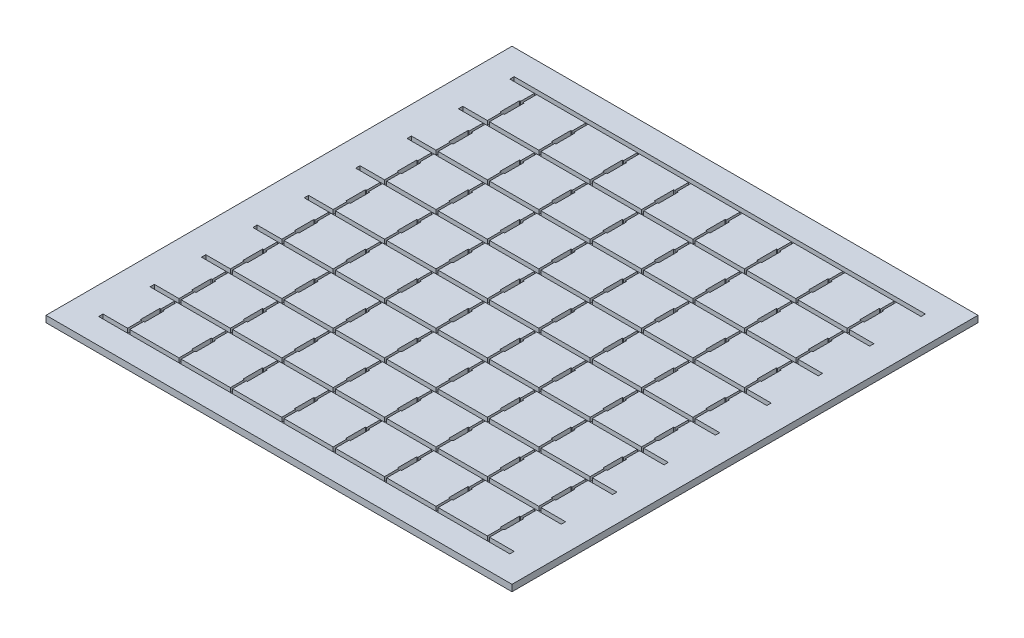
SolidWorks part; units mm, degrees
material "Acrylic (Medium-high impact)"
ref_plane "Front Plane" through (0, 0, 0) normal (0, 0, 1) x (1, 0, 0)
ref_plane "Top Plane" through (0, 0, 0) normal (0, 1, 0) x (1, 0, 0)
ref_plane "Right Plane" through (0, 0, 0) normal (1, 0, 0) x (0, 0, -1)
sketch "Sketch1" plane through (0, 0, 0) normal (0, 1, 0) x (1, 0, 0)
  line L1 (0, 0) -> (431.8, 0)
  line L2 (0, 0) -> (0, 431.8)
  line L3 (0, 431.8) -> (431.8, 431.8)
  line L4 (431.8, 0) -> (431.8, 431.8)
  dimension "D1" = 431.8
  dimension "D2" = 431.8
extrude "Boss-Extrude1" add sketch "Sketch1" along normal blind 6
sketch "Sketch2" plane through (0, 6, 0) normal (0, 1, 0) x (1, 0, 0)
  line L0 (73.025, 25.4) -> (73.025, 73.025) construction
  line L1 (25.4, 25.4) -> (73.025, 25.4) construction
  line L2 (25.4, 25.4) -> (25.4, 73.025) construction
  line L3 (25.4, 73.025) -> (73.025, 73.025) construction
  line L4 (73.025, 25.4) -> (73.025, 73.025) construction
  line L5 (73.025, 25.4) -> (120.65, 25.4) construction
  line L6 (120.65, 25.4) -> (120.65, 73.025) construction
  line L7 (73.025, 73.025) -> (120.65, 73.025) construction
  line L8 (120.65, 25.4) -> (120.65, 73.025) construction
  line L9 (120.65, 25.4) -> (168.275, 25.4) construction
  line L10 (168.275, 25.4) -> (168.275, 73.025) construction
  line L11 (120.65, 73.025) -> (168.275, 73.025) construction
  line L12 (168.275, 25.4) -> (168.275, 73.025) construction
  line L13 (168.275, 25.4) -> (215.9, 25.4) construction
  line L14 (215.9, 25.4) -> (215.9, 73.025) construction
  line L15 (168.275, 73.025) -> (215.9, 73.025) construction
  line L16 (215.9, 25.4) -> (215.9, 73.025) construction
  line L17 (215.9, 25.4) -> (263.525, 25.4) construction
  line L18 (263.525, 25.4) -> (263.525, 73.025) construction
  line L19 (215.9, 73.025) -> (263.525, 73.025) construction
  line L20 (263.525, 25.4) -> (263.525, 73.025) construction
  line L21 (263.525, 25.4) -> (311.15, 25.4) construction
  line L22 (311.15, 25.4) -> (311.15, 73.025) construction
  line L23 (263.525, 73.025) -> (311.15, 73.025) construction
  line L24 (311.15, 25.4) -> (311.15, 73.025) construction
  line L25 (311.15, 25.4) -> (358.775, 25.4) construction
  line L26 (358.775, 25.4) -> (358.775, 73.025) construction
  line L27 (311.15, 73.025) -> (358.775, 73.025) construction
  line L28 (358.775, 25.4) -> (358.775, 73.025) construction
  line L29 (358.775, 25.4) -> (406.4, 25.4) construction
  line L30 (406.4, 25.4) -> (406.4, 73.025) construction
  line L31 (358.775, 73.025) -> (406.4, 73.025) construction
  line L32 (73.025, 73.025) -> (73.025, 120.65) construction
  line L33 (73.025, 73.025) -> (120.65, 73.025) construction
  line L34 (120.65, 73.025) -> (120.65, 120.65) construction
  line L35 (73.025, 120.65) -> (120.65, 120.65) construction
  line L36 (120.65, 73.025) -> (120.65, 120.65) construction
  line L37 (120.65, 73.025) -> (168.275, 73.025) construction
  line L38 (168.275, 73.025) -> (168.275, 120.65) construction
  line L39 (120.65, 120.65) -> (168.275, 120.65) construction
  line L40 (168.275, 73.025) -> (168.275, 120.65) construction
  line L41 (168.275, 73.025) -> (215.9, 73.025) construction
  line L42 (215.9, 73.025) -> (215.9, 120.65) construction
  line L43 (168.275, 120.65) -> (215.9, 120.65) construction
  line L44 (215.9, 73.025) -> (215.9, 120.65) construction
  line L45 (215.9, 73.025) -> (263.525, 73.025) construction
  line L46 (263.525, 73.025) -> (263.525, 120.65) construction
  line L47 (215.9, 120.65) -> (263.525, 120.65) construction
  line L48 (263.525, 73.025) -> (263.525, 120.65) construction
  line L49 (263.525, 73.025) -> (311.15, 73.025) construction
  line L50 (311.15, 73.025) -> (311.15, 120.65) construction
  line L51 (263.525, 120.65) -> (311.15, 120.65) construction
  line L52 (311.15, 73.025) -> (311.15, 120.65) construction
  line L53 (311.15, 73.025) -> (358.775, 73.025) construction
  line L54 (358.775, 73.025) -> (358.775, 120.65) construction
  line L55 (311.15, 120.65) -> (358.775, 120.65) construction
  line L56 (358.775, 73.025) -> (358.775, 120.65) construction
  line L57 (358.775, 73.025) -> (406.4, 73.025) construction
  line L58 (406.4, 73.025) -> (406.4, 120.65) construction
  line L59 (358.775, 120.65) -> (406.4, 120.65) construction
  line L60 (73.025, 120.65) -> (73.025, 168.275) construction
  line L61 (73.025, 120.65) -> (120.65, 120.65) construction
  line L62 (120.65, 120.65) -> (120.65, 168.275) construction
  line L63 (73.025, 168.275) -> (120.65, 168.275) construction
  line L64 (120.65, 120.65) -> (120.65, 168.275) construction
  line L65 (120.65, 120.65) -> (168.275, 120.65) construction
  line L66 (168.275, 120.65) -> (168.275, 168.275) construction
  line L67 (120.65, 168.275) -> (168.275, 168.275) construction
  line L68 (168.275, 120.65) -> (168.275, 168.275) construction
  line L69 (168.275, 120.65) -> (215.9, 120.65) construction
  line L70 (215.9, 120.65) -> (215.9, 168.275) construction
  line L71 (168.275, 168.275) -> (215.9, 168.275) construction
  line L72 (215.9, 120.65) -> (215.9, 168.275) construction
  line L73 (215.9, 120.65) -> (263.525, 120.65) construction
  line L74 (263.525, 120.65) -> (263.525, 168.275) construction
  line L75 (215.9, 168.275) -> (263.525, 168.275) construction
  line L76 (263.525, 120.65) -> (263.525, 168.275) construction
  line L77 (263.525, 120.65) -> (311.15, 120.65) construction
  line L78 (311.15, 120.65) -> (311.15, 168.275) construction
  line L79 (263.525, 168.275) -> (311.15, 168.275) construction
  line L80 (311.15, 120.65) -> (311.15, 168.275) construction
  line L81 (311.15, 120.65) -> (358.775, 120.65) construction
  line L82 (358.775, 120.65) -> (358.775, 168.275) construction
  line L83 (311.15, 168.275) -> (358.775, 168.275) construction
  line L84 (358.775, 120.65) -> (358.775, 168.275) construction
  line L85 (358.775, 120.65) -> (406.4, 120.65) construction
  line L86 (406.4, 120.65) -> (406.4, 168.275) construction
  line L87 (358.775, 168.275) -> (406.4, 168.275) construction
  line L88 (73.025, 168.275) -> (73.025, 215.9) construction
  line L89 (73.025, 168.275) -> (120.65, 168.275) construction
  line L90 (120.65, 168.275) -> (120.65, 215.9) construction
  line L91 (73.025, 215.9) -> (120.65, 215.9) construction
  line L92 (120.65, 168.275) -> (120.65, 215.9) construction
  line L93 (120.65, 168.275) -> (168.275, 168.275) construction
  line L94 (168.275, 168.275) -> (168.275, 215.9) construction
  line L95 (120.65, 215.9) -> (168.275, 215.9) construction
  line L96 (168.275, 168.275) -> (168.275, 215.9) construction
  line L97 (168.275, 168.275) -> (215.9, 168.275) construction
  line L98 (215.9, 168.275) -> (215.9, 215.9) construction
  line L99 (168.275, 215.9) -> (215.9, 215.9) construction
  line L100 (215.9, 168.275) -> (215.9, 215.9) construction
  line L101 (215.9, 168.275) -> (263.525, 168.275) construction
  line L102 (263.525, 168.275) -> (263.525, 215.9) construction
  line L103 (215.9, 215.9) -> (263.525, 215.9) construction
  line L104 (263.525, 168.275) -> (263.525, 215.9) construction
  line L105 (263.525, 168.275) -> (311.15, 168.275) construction
  line L106 (311.15, 168.275) -> (311.15, 215.9) construction
  line L107 (263.525, 215.9) -> (311.15, 215.9) construction
  line L108 (311.15, 168.275) -> (311.15, 215.9) construction
  line L109 (311.15, 168.275) -> (358.775, 168.275) construction
  line L110 (358.775, 168.275) -> (358.775, 215.9) construction
  line L111 (311.15, 215.9) -> (358.775, 215.9) construction
  line L112 (358.775, 168.275) -> (358.775, 215.9) construction
  line L113 (358.775, 168.275) -> (406.4, 168.275) construction
  line L114 (406.4, 168.275) -> (406.4, 215.9) construction
  line L115 (358.775, 215.9) -> (406.4, 215.9) construction
  line L116 (73.025, 215.9) -> (73.025, 263.525) construction
  line L117 (73.025, 215.9) -> (120.65, 215.9) construction
  line L118 (120.65, 215.9) -> (120.65, 263.525) construction
  line L119 (73.025, 263.525) -> (120.65, 263.525) construction
  line L120 (120.65, 215.9) -> (120.65, 263.525) construction
  line L121 (120.65, 215.9) -> (168.275, 215.9) construction
  line L122 (168.275, 215.9) -> (168.275, 263.525) construction
  line L123 (120.65, 263.525) -> (168.275, 263.525) construction
  line L124 (168.275, 215.9) -> (168.275, 263.525) construction
  line L125 (168.275, 215.9) -> (215.9, 215.9) construction
  line L126 (215.9, 215.9) -> (215.9, 263.525) construction
  line L127 (168.275, 263.525) -> (215.9, 263.525) construction
  line L128 (215.9, 215.9) -> (215.9, 263.525) construction
  line L129 (215.9, 215.9) -> (263.525, 215.9) construction
  line L130 (263.525, 215.9) -> (263.525, 263.525) construction
  line L131 (215.9, 263.525) -> (263.525, 263.525) construction
  line L132 (263.525, 215.9) -> (263.525, 263.525) construction
  line L133 (263.525, 215.9) -> (311.15, 215.9) construction
  line L134 (311.15, 215.9) -> (311.15, 263.525) construction
  line L135 (263.525, 263.525) -> (311.15, 263.525) construction
  line L136 (311.15, 215.9) -> (311.15, 263.525) construction
  line L137 (311.15, 215.9) -> (358.775, 215.9) construction
  line L138 (358.775, 215.9) -> (358.775, 263.525) construction
  line L139 (311.15, 263.525) -> (358.775, 263.525) construction
  line L140 (358.775, 215.9) -> (358.775, 263.525) construction
  line L141 (358.775, 215.9) -> (406.4, 215.9) construction
  line L142 (406.4, 215.9) -> (406.4, 263.525) construction
  line L143 (358.775, 263.525) -> (406.4, 263.525) construction
  line L144 (73.025, 263.525) -> (73.025, 311.15) construction
  line L145 (73.025, 263.525) -> (120.65, 263.525) construction
  line L146 (120.65, 263.525) -> (120.65, 311.15) construction
  line L147 (73.025, 311.15) -> (120.65, 311.15) construction
  line L148 (120.65, 263.525) -> (120.65, 311.15) construction
  line L149 (120.65, 263.525) -> (168.275, 263.525) construction
  line L150 (168.275, 263.525) -> (168.275, 311.15) construction
  line L151 (120.65, 311.15) -> (168.275, 311.15) construction
  line L152 (168.275, 263.525) -> (168.275, 311.15) construction
  line L153 (168.275, 263.525) -> (215.9, 263.525) construction
  line L154 (215.9, 263.525) -> (215.9, 311.15) construction
  line L155 (168.275, 311.15) -> (215.9, 311.15) construction
  line L156 (215.9, 263.525) -> (215.9, 311.15) construction
  line L157 (215.9, 263.525) -> (263.525, 263.525) construction
  line L158 (263.525, 263.525) -> (263.525, 311.15) construction
  line L159 (215.9, 311.15) -> (263.525, 311.15) construction
  line L160 (263.525, 263.525) -> (263.525, 311.15) construction
  line L161 (263.525, 263.525) -> (311.15, 263.525) construction
  line L162 (311.15, 263.525) -> (311.15, 311.15) construction
  line L163 (263.525, 311.15) -> (311.15, 311.15) construction
  line L164 (311.15, 263.525) -> (311.15, 311.15) construction
  line L165 (311.15, 263.525) -> (358.775, 263.525) construction
  line L166 (358.775, 263.525) -> (358.775, 311.15) construction
  line L167 (311.15, 311.15) -> (358.775, 311.15) construction
  line L168 (358.775, 263.525) -> (358.775, 311.15) construction
  line L169 (358.775, 263.525) -> (406.4, 263.525) construction
  line L170 (406.4, 263.525) -> (406.4, 311.15) construction
  line L171 (358.775, 311.15) -> (406.4, 311.15) construction
  line L172 (73.025, 311.15) -> (73.025, 358.775) construction
  line L173 (73.025, 311.15) -> (120.65, 311.15) construction
  line L174 (120.65, 311.15) -> (120.65, 358.775) construction
  line L175 (73.025, 358.775) -> (120.65, 358.775) construction
  line L176 (120.65, 311.15) -> (120.65, 358.775) construction
  line L177 (120.65, 311.15) -> (168.275, 311.15) construction
  line L178 (168.275, 311.15) -> (168.275, 358.775) construction
  line L179 (120.65, 358.775) -> (168.275, 358.775) construction
  line L180 (168.275, 311.15) -> (168.275, 358.775) construction
  line L181 (168.275, 311.15) -> (215.9, 311.15) construction
  line L182 (215.9, 311.15) -> (215.9, 358.775) construction
  line L183 (168.275, 358.775) -> (215.9, 358.775) construction
  line L184 (215.9, 311.15) -> (215.9, 358.775) construction
  line L185 (215.9, 311.15) -> (263.525, 311.15) construction
  line L186 (263.525, 311.15) -> (263.525, 358.775) construction
  line L187 (215.9, 358.775) -> (263.525, 358.775) construction
  line L188 (263.525, 311.15) -> (263.525, 358.775) construction
  line L189 (263.525, 311.15) -> (311.15, 311.15) construction
  line L190 (311.15, 311.15) -> (311.15, 358.775) construction
  line L191 (263.525, 358.775) -> (311.15, 358.775) construction
  line L192 (311.15, 311.15) -> (311.15, 358.775) construction
  line L193 (311.15, 311.15) -> (358.775, 311.15) construction
  line L194 (358.775, 311.15) -> (358.775, 358.775) construction
  line L195 (311.15, 358.775) -> (358.775, 358.775) construction
  line L196 (358.775, 311.15) -> (358.775, 358.775) construction
  line L197 (358.775, 311.15) -> (406.4, 311.15) construction
  line L198 (406.4, 311.15) -> (406.4, 358.775) construction
  line L199 (358.775, 358.775) -> (406.4, 358.775) construction
  line L200 (73.025, 358.775) -> (73.025, 406.4) construction
  line L201 (73.025, 358.775) -> (120.65, 358.775) construction
  line L202 (120.65, 358.775) -> (120.65, 406.4) construction
  line L203 (73.025, 406.4) -> (120.65, 406.4) construction
  line L204 (120.65, 358.775) -> (120.65, 406.4) construction
  line L205 (120.65, 358.775) -> (168.275, 358.775) construction
  line L206 (168.275, 358.775) -> (168.275, 406.4) construction
  line L207 (120.65, 406.4) -> (168.275, 406.4) construction
  line L208 (168.275, 358.775) -> (168.275, 406.4) construction
  line L209 (168.275, 358.775) -> (215.9, 358.775) construction
  line L210 (215.9, 358.775) -> (215.9, 406.4) construction
  line L211 (168.275, 406.4) -> (215.9, 406.4) construction
  line L212 (215.9, 358.775) -> (215.9, 406.4) construction
  line L213 (215.9, 358.775) -> (263.525, 358.775) construction
  line L214 (263.525, 358.775) -> (263.525, 406.4) construction
  line L215 (215.9, 406.4) -> (263.525, 406.4) construction
  line L216 (263.525, 358.775) -> (263.525, 406.4) construction
  line L217 (263.525, 358.775) -> (311.15, 358.775) construction
  line L218 (311.15, 358.775) -> (311.15, 406.4) construction
  line L219 (263.525, 406.4) -> (311.15, 406.4) construction
  line L220 (311.15, 358.775) -> (311.15, 406.4) construction
  line L221 (311.15, 358.775) -> (358.775, 358.775) construction
  line L222 (358.775, 358.775) -> (358.775, 406.4) construction
  line L223 (311.15, 406.4) -> (358.775, 406.4) construction
  line L224 (358.775, 358.775) -> (358.775, 406.4) construction
  line L225 (358.775, 358.775) -> (406.4, 358.775) construction
  line L226 (406.4, 358.775) -> (406.4, 406.4) construction
  line L227 (358.775, 406.4) -> (406.4, 406.4) construction
  line L228 (25.4, 73.025) -> (25.4, 120.65) construction
  line L229 (25.4, 73.025) -> (73.025, 73.025) construction
  line L230 (73.025, 73.025) -> (73.025, 120.65) construction
  line L231 (25.4, 120.65) -> (73.025, 120.65) construction
  line L232 (25.4, 120.65) -> (25.4, 168.275) construction
  line L233 (25.4, 120.65) -> (73.025, 120.65) construction
  line L234 (73.025, 120.65) -> (73.025, 168.275) construction
  line L235 (25.4, 168.275) -> (73.025, 168.275) construction
  line L236 (25.4, 168.275) -> (25.4, 215.9) construction
  line L237 (25.4, 168.275) -> (73.025, 168.275) construction
  line L238 (73.025, 168.275) -> (73.025, 215.9) construction
  line L239 (25.4, 215.9) -> (73.025, 215.9) construction
  line L240 (25.4, 215.9) -> (25.4, 263.525) construction
  line L241 (25.4, 215.9) -> (73.025, 215.9) construction
  line L242 (73.025, 215.9) -> (73.025, 263.525) construction
  line L243 (25.4, 263.525) -> (73.025, 263.525) construction
  line L244 (25.4, 263.525) -> (25.4, 311.15) construction
  line L245 (25.4, 263.525) -> (73.025, 263.525) construction
  line L246 (73.025, 263.525) -> (73.025, 311.15) construction
  line L247 (25.4, 311.15) -> (73.025, 311.15) construction
  line L248 (25.4, 311.15) -> (25.4, 358.775) construction
  line L249 (25.4, 311.15) -> (73.025, 311.15) construction
  line L250 (73.025, 311.15) -> (73.025, 358.775) construction
  line L251 (25.4, 358.775) -> (73.025, 358.775) construction
  line L252 (25.4, 358.775) -> (25.4, 406.4) construction
  line L253 (25.4, 358.775) -> (73.025, 358.775) construction
  line L254 (73.025, 358.775) -> (73.025, 406.4) construction
  line L255 (25.4, 406.4) -> (73.025, 406.4) construction
  line L256 (0, 0) -> (431.8, 0) construction
  line L257 (0, 431.8) -> (0, 0) construction
  line L258 (50.2125, 58.2125) -> (51.2125, 58.2125)
  line L259 (431.8, 431.8) -> (0, 431.8) construction
  line L260 (431.8, 0) -> (431.8, 431.8) construction
  line L261 (49.2125, 25.4) -> (49.2125, 73.025) construction
  line L262 (47.2125, 58.2125) -> (48.2125, 58.2125)
  line L263 (47.2125, 58.2125) -> (47.2125, 40.2125)
  line L264 (47.2125, 40.2125) -> (48.2125, 40.2125)
  line L265 (51.2125, 58.2125) -> (51.2125, 40.2125)
  line L266 (25.4, 49.2125) -> (73.025, 49.2125) construction
  line L267 (50.2125, 40.2125) -> (51.2125, 40.2125)
  line L269 (50.2125, 58.2125) -> (50.2125, 73.025)
  line L271 (48.2125, 58.2125) -> (48.2125, 73.025)
  line L273 (48.2125, 40.2125) -> (48.2125, 25.4)
  line L274 (48.2125, 25.4) -> (50.2125, 25.4)
  line L275 (50.2125, 40.2125) -> (50.2125, 25.4)
  line L276 (48.2125, 105.8375) -> (48.2125, 120.65)
  line L277 (50.2125, 105.8375) -> (50.2125, 120.65)
  line L278 (47.2125, 105.8375) -> (47.2125, 87.8375)
  line L279 (47.2125, 105.8375) -> (48.2125, 105.8375)
  line L280 (50.2125, 105.8375) -> (51.2125, 105.8375)
  line L281 (51.2125, 105.8375) -> (51.2125, 87.8375)
  line L282 (50.2125, 87.8375) -> (51.2125, 87.8375)
  line L283 (50.2125, 87.8375) -> (50.2125, 73.025)
  line L284 (48.2125, 87.8375) -> (48.2125, 73.025)
  line L285 (47.2125, 87.8375) -> (48.2125, 87.8375)
  line L286 (48.2125, 153.4625) -> (48.2125, 168.275)
  line L287 (50.2125, 153.4625) -> (50.2125, 168.275)
  line L288 (47.2125, 153.4625) -> (47.2125, 135.4625)
  line L289 (47.2125, 153.4625) -> (48.2125, 153.4625)
  line L290 (50.2125, 153.4625) -> (51.2125, 153.4625)
  line L291 (51.2125, 153.4625) -> (51.2125, 135.4625)
  line L292 (50.2125, 135.4625) -> (51.2125, 135.4625)
  line L293 (50.2125, 135.4625) -> (50.2125, 120.65)
  line L294 (48.2125, 135.4625) -> (48.2125, 120.65)
  line L295 (47.2125, 135.4625) -> (48.2125, 135.4625)
  line L296 (48.2125, 201.0875) -> (48.2125, 215.9)
  line L297 (50.2125, 201.0875) -> (50.2125, 215.9)
  line L298 (47.2125, 201.0875) -> (47.2125, 183.0875)
  line L299 (47.2125, 201.0875) -> (48.2125, 201.0875)
  line L300 (50.2125, 201.0875) -> (51.2125, 201.0875)
  line L301 (51.2125, 201.0875) -> (51.2125, 183.0875)
  line L302 (50.2125, 183.0875) -> (51.2125, 183.0875)
  line L303 (50.2125, 183.0875) -> (50.2125, 168.275)
  line L304 (48.2125, 183.0875) -> (48.2125, 168.275)
  line L305 (47.2125, 183.0875) -> (48.2125, 183.0875)
  line L306 (48.2125, 248.7125) -> (48.2125, 263.525)
  line L307 (50.2125, 248.7125) -> (50.2125, 263.525)
  line L308 (47.2125, 248.7125) -> (47.2125, 230.7125)
  line L309 (47.2125, 248.7125) -> (48.2125, 248.7125)
  line L310 (50.2125, 248.7125) -> (51.2125, 248.7125)
  line L311 (51.2125, 248.7125) -> (51.2125, 230.7125)
  line L312 (50.2125, 230.7125) -> (51.2125, 230.7125)
  line L313 (50.2125, 230.7125) -> (50.2125, 215.9)
  line L314 (48.2125, 230.7125) -> (48.2125, 215.9)
  line L315 (47.2125, 230.7125) -> (48.2125, 230.7125)
  line L316 (48.2125, 296.3375) -> (48.2125, 311.15)
  line L317 (50.2125, 296.3375) -> (50.2125, 311.15)
  line L318 (47.2125, 296.3375) -> (47.2125, 278.3375)
  line L319 (47.2125, 296.3375) -> (48.2125, 296.3375)
  line L320 (50.2125, 296.3375) -> (51.2125, 296.3375)
  line L321 (51.2125, 296.3375) -> (51.2125, 278.3375)
  line L322 (50.2125, 278.3375) -> (51.2125, 278.3375)
  line L323 (50.2125, 278.3375) -> (50.2125, 263.525)
  line L324 (48.2125, 278.3375) -> (48.2125, 263.525)
  line L325 (47.2125, 278.3375) -> (48.2125, 278.3375)
  line L326 (48.2125, 343.9625) -> (48.2125, 358.775)
  line L327 (50.2125, 343.9625) -> (50.2125, 358.775)
  line L328 (47.2125, 343.9625) -> (47.2125, 325.9625)
  line L329 (47.2125, 343.9625) -> (48.2125, 343.9625)
  line L330 (50.2125, 343.9625) -> (51.2125, 343.9625)
  line L331 (51.2125, 343.9625) -> (51.2125, 325.9625)
  line L332 (50.2125, 325.9625) -> (51.2125, 325.9625)
  line L333 (50.2125, 325.9625) -> (50.2125, 311.15)
  line L334 (48.2125, 325.9625) -> (48.2125, 311.15)
  line L335 (47.2125, 325.9625) -> (48.2125, 325.9625)
  line L336 (48.2125, 391.5875) -> (48.2125, 406.4)
  line L337 (50.2125, 391.5875) -> (50.2125, 406.4)
  line L338 (47.2125, 391.5875) -> (47.2125, 373.5875)
  line L339 (47.2125, 391.5875) -> (48.2125, 391.5875)
  line L340 (50.2125, 391.5875) -> (51.2125, 391.5875)
  line L341 (51.2125, 391.5875) -> (51.2125, 373.5875)
  line L342 (50.2125, 373.5875) -> (51.2125, 373.5875)
  line L343 (50.2125, 373.5875) -> (50.2125, 358.775)
  line L344 (48.2125, 373.5875) -> (48.2125, 358.775)
  line L345 (47.2125, 373.5875) -> (48.2125, 373.5875)
  line L346 (95.8375, 105.8375) -> (95.8375, 120.65)
  line L347 (97.8375, 105.8375) -> (97.8375, 120.65)
  line L348 (94.8375, 105.8375) -> (94.8375, 87.8375)
  line L349 (94.8375, 105.8375) -> (95.8375, 105.8375)
  line L350 (97.8375, 105.8375) -> (98.8375, 105.8375)
  line L351 (98.8375, 105.8375) -> (98.8375, 87.8375)
  line L352 (97.8375, 87.8375) -> (98.8375, 87.8375)
  line L353 (97.8375, 87.8375) -> (97.8375, 73.025)
  line L354 (95.8375, 87.8375) -> (95.8375, 73.025)
  line L355 (94.8375, 87.8375) -> (95.8375, 87.8375)
  line L356 (95.8375, 153.4625) -> (95.8375, 168.275)
  line L357 (97.8375, 153.4625) -> (97.8375, 168.275)
  line L358 (94.8375, 153.4625) -> (94.8375, 135.4625)
  line L359 (94.8375, 153.4625) -> (95.8375, 153.4625)
  line L360 (97.8375, 153.4625) -> (98.8375, 153.4625)
  line L361 (98.8375, 153.4625) -> (98.8375, 135.4625)
  line L362 (97.8375, 135.4625) -> (98.8375, 135.4625)
  line L363 (97.8375, 135.4625) -> (97.8375, 120.65)
  line L364 (95.8375, 135.4625) -> (95.8375, 120.65)
  line L365 (94.8375, 135.4625) -> (95.8375, 135.4625)
  line L366 (95.8375, 201.0875) -> (95.8375, 215.9)
  line L367 (97.8375, 201.0875) -> (97.8375, 215.9)
  line L368 (94.8375, 201.0875) -> (94.8375, 183.0875)
  line L369 (94.8375, 201.0875) -> (95.8375, 201.0875)
  line L370 (97.8375, 201.0875) -> (98.8375, 201.0875)
  line L371 (98.8375, 201.0875) -> (98.8375, 183.0875)
  line L372 (97.8375, 183.0875) -> (98.8375, 183.0875)
  line L373 (97.8375, 183.0875) -> (97.8375, 168.275)
  line L374 (95.8375, 183.0875) -> (95.8375, 168.275)
  line L375 (94.8375, 183.0875) -> (95.8375, 183.0875)
  line L376 (95.8375, 248.7125) -> (95.8375, 263.525)
  line L377 (97.8375, 248.7125) -> (97.8375, 263.525)
  line L378 (94.8375, 248.7125) -> (94.8375, 230.7125)
  line L379 (94.8375, 248.7125) -> (95.8375, 248.7125)
  line L380 (97.8375, 248.7125) -> (98.8375, 248.7125)
  line L381 (98.8375, 248.7125) -> (98.8375, 230.7125)
  line L382 (97.8375, 230.7125) -> (98.8375, 230.7125)
  line L383 (97.8375, 230.7125) -> (97.8375, 215.9)
  line L384 (95.8375, 230.7125) -> (95.8375, 215.9)
  line L385 (94.8375, 230.7125) -> (95.8375, 230.7125)
  line L386 (95.8375, 296.3375) -> (95.8375, 311.15)
  line L387 (97.8375, 296.3375) -> (97.8375, 311.15)
  line L388 (94.8375, 296.3375) -> (94.8375, 278.3375)
  line L389 (94.8375, 296.3375) -> (95.8375, 296.3375)
  line L390 (97.8375, 296.3375) -> (98.8375, 296.3375)
  line L391 (98.8375, 296.3375) -> (98.8375, 278.3375)
  line L392 (97.8375, 278.3375) -> (98.8375, 278.3375)
  line L393 (97.8375, 278.3375) -> (97.8375, 263.525)
  line L394 (95.8375, 278.3375) -> (95.8375, 263.525)
  line L395 (94.8375, 278.3375) -> (95.8375, 278.3375)
  line L396 (95.8375, 343.9625) -> (95.8375, 358.775)
  line L397 (97.8375, 343.9625) -> (97.8375, 358.775)
  line L398 (94.8375, 343.9625) -> (94.8375, 325.9625)
  line L399 (94.8375, 343.9625) -> (95.8375, 343.9625)
  line L400 (97.8375, 343.9625) -> (98.8375, 343.9625)
  line L401 (98.8375, 343.9625) -> (98.8375, 325.9625)
  line L402 (97.8375, 325.9625) -> (98.8375, 325.9625)
  line L403 (97.8375, 325.9625) -> (97.8375, 311.15)
  line L404 (95.8375, 325.9625) -> (95.8375, 311.15)
  line L405 (94.8375, 325.9625) -> (95.8375, 325.9625)
  line L406 (95.8375, 391.5875) -> (95.8375, 406.4)
  line L407 (97.8375, 391.5875) -> (97.8375, 406.4)
  line L408 (94.8375, 391.5875) -> (94.8375, 373.5875)
  line L409 (94.8375, 391.5875) -> (95.8375, 391.5875)
  line L410 (97.8375, 391.5875) -> (98.8375, 391.5875)
  line L411 (98.8375, 391.5875) -> (98.8375, 373.5875)
  line L412 (97.8375, 373.5875) -> (98.8375, 373.5875)
  line L413 (97.8375, 373.5875) -> (97.8375, 358.775)
  line L414 (95.8375, 373.5875) -> (95.8375, 358.775)
  line L415 (94.8375, 373.5875) -> (95.8375, 373.5875)
  line L416 (143.4625, 105.8375) -> (143.4625, 120.65)
  line L417 (145.4625, 105.8375) -> (145.4625, 120.65)
  line L418 (142.4625, 105.8375) -> (142.4625, 87.8375)
  line L419 (142.4625, 105.8375) -> (143.4625, 105.8375)
  line L420 (145.4625, 105.8375) -> (146.4625, 105.8375)
  line L421 (146.4625, 105.8375) -> (146.4625, 87.8375)
  line L422 (145.4625, 87.8375) -> (146.4625, 87.8375)
  line L423 (145.4625, 87.8375) -> (145.4625, 73.025)
  line L424 (143.4625, 87.8375) -> (143.4625, 73.025)
  line L425 (142.4625, 87.8375) -> (143.4625, 87.8375)
  line L426 (143.4625, 153.4625) -> (143.4625, 168.275)
  line L427 (145.4625, 153.4625) -> (145.4625, 168.275)
  line L428 (142.4625, 153.4625) -> (142.4625, 135.4625)
  line L429 (142.4625, 153.4625) -> (143.4625, 153.4625)
  line L430 (145.4625, 153.4625) -> (146.4625, 153.4625)
  line L431 (146.4625, 153.4625) -> (146.4625, 135.4625)
  line L432 (145.4625, 135.4625) -> (146.4625, 135.4625)
  line L433 (145.4625, 135.4625) -> (145.4625, 120.65)
  line L434 (143.4625, 135.4625) -> (143.4625, 120.65)
  line L435 (142.4625, 135.4625) -> (143.4625, 135.4625)
  line L436 (143.4625, 201.0875) -> (143.4625, 215.9)
  line L437 (145.4625, 201.0875) -> (145.4625, 215.9)
  line L438 (142.4625, 201.0875) -> (142.4625, 183.0875)
  line L439 (142.4625, 201.0875) -> (143.4625, 201.0875)
  line L440 (145.4625, 201.0875) -> (146.4625, 201.0875)
  line L441 (146.4625, 201.0875) -> (146.4625, 183.0875)
  line L442 (145.4625, 183.0875) -> (146.4625, 183.0875)
  line L443 (145.4625, 183.0875) -> (145.4625, 168.275)
  line L444 (143.4625, 183.0875) -> (143.4625, 168.275)
  line L445 (142.4625, 183.0875) -> (143.4625, 183.0875)
  line L446 (143.4625, 248.7125) -> (143.4625, 263.525)
  line L447 (145.4625, 248.7125) -> (145.4625, 263.525)
  line L448 (142.4625, 248.7125) -> (142.4625, 230.7125)
  line L449 (142.4625, 248.7125) -> (143.4625, 248.7125)
  line L450 (145.4625, 248.7125) -> (146.4625, 248.7125)
  line L451 (146.4625, 248.7125) -> (146.4625, 230.7125)
  line L452 (145.4625, 230.7125) -> (146.4625, 230.7125)
  line L453 (145.4625, 230.7125) -> (145.4625, 215.9)
  line L454 (143.4625, 230.7125) -> (143.4625, 215.9)
  line L455 (142.4625, 230.7125) -> (143.4625, 230.7125)
  line L456 (143.4625, 296.3375) -> (143.4625, 311.15)
  line L457 (145.4625, 296.3375) -> (145.4625, 311.15)
  line L458 (142.4625, 296.3375) -> (142.4625, 278.3375)
  line L459 (142.4625, 296.3375) -> (143.4625, 296.3375)
  line L460 (145.4625, 296.3375) -> (146.4625, 296.3375)
  line L461 (146.4625, 296.3375) -> (146.4625, 278.3375)
  line L462 (145.4625, 278.3375) -> (146.4625, 278.3375)
  line L463 (145.4625, 278.3375) -> (145.4625, 263.525)
  line L464 (143.4625, 278.3375) -> (143.4625, 263.525)
  line L465 (142.4625, 278.3375) -> (143.4625, 278.3375)
  line L466 (143.4625, 343.9625) -> (143.4625, 358.775)
  line L467 (145.4625, 343.9625) -> (145.4625, 358.775)
  line L468 (142.4625, 343.9625) -> (142.4625, 325.9625)
  line L469 (142.4625, 343.9625) -> (143.4625, 343.9625)
  line L470 (145.4625, 343.9625) -> (146.4625, 343.9625)
  line L471 (146.4625, 343.9625) -> (146.4625, 325.9625)
  line L472 (145.4625, 325.9625) -> (146.4625, 325.9625)
  line L473 (145.4625, 325.9625) -> (145.4625, 311.15)
  line L474 (143.4625, 325.9625) -> (143.4625, 311.15)
  line L475 (142.4625, 325.9625) -> (143.4625, 325.9625)
  line L476 (143.4625, 391.5875) -> (143.4625, 406.4)
  line L477 (145.4625, 391.5875) -> (145.4625, 406.4)
  line L478 (142.4625, 391.5875) -> (142.4625, 373.5875)
  line L479 (142.4625, 391.5875) -> (143.4625, 391.5875)
  line L480 (145.4625, 391.5875) -> (146.4625, 391.5875)
  line L481 (146.4625, 391.5875) -> (146.4625, 373.5875)
  line L482 (145.4625, 373.5875) -> (146.4625, 373.5875)
  line L483 (145.4625, 373.5875) -> (145.4625, 358.775)
  line L484 (143.4625, 373.5875) -> (143.4625, 358.775)
  line L485 (142.4625, 373.5875) -> (143.4625, 373.5875)
  line L486 (191.0875, 105.8375) -> (191.0875, 120.65)
  line L487 (193.0875, 105.8375) -> (193.0875, 120.65)
  line L488 (190.0875, 105.8375) -> (190.0875, 87.8375)
  line L489 (190.0875, 105.8375) -> (191.0875, 105.8375)
  line L490 (193.0875, 105.8375) -> (194.0875, 105.8375)
  line L491 (194.0875, 105.8375) -> (194.0875, 87.8375)
  line L492 (193.0875, 87.8375) -> (194.0875, 87.8375)
  line L493 (193.0875, 87.8375) -> (193.0875, 73.025)
  line L494 (191.0875, 87.8375) -> (191.0875, 73.025)
  line L495 (190.0875, 87.8375) -> (191.0875, 87.8375)
  line L496 (191.0875, 153.4625) -> (191.0875, 168.275)
  line L497 (193.0875, 153.4625) -> (193.0875, 168.275)
  line L498 (190.0875, 153.4625) -> (190.0875, 135.4625)
  line L499 (190.0875, 153.4625) -> (191.0875, 153.4625)
  line L500 (193.0875, 153.4625) -> (194.0875, 153.4625)
  line L501 (194.0875, 153.4625) -> (194.0875, 135.4625)
  line L502 (193.0875, 135.4625) -> (194.0875, 135.4625)
  line L503 (193.0875, 135.4625) -> (193.0875, 120.65)
  line L504 (191.0875, 135.4625) -> (191.0875, 120.65)
  line L505 (190.0875, 135.4625) -> (191.0875, 135.4625)
  line L506 (191.0875, 201.0875) -> (191.0875, 215.9)
  line L507 (193.0875, 201.0875) -> (193.0875, 215.9)
  line L508 (190.0875, 201.0875) -> (190.0875, 183.0875)
  line L509 (190.0875, 201.0875) -> (191.0875, 201.0875)
  line L510 (193.0875, 201.0875) -> (194.0875, 201.0875)
  line L511 (194.0875, 201.0875) -> (194.0875, 183.0875)
  line L512 (193.0875, 183.0875) -> (194.0875, 183.0875)
  line L513 (193.0875, 183.0875) -> (193.0875, 168.275)
  line L514 (191.0875, 183.0875) -> (191.0875, 168.275)
  line L515 (190.0875, 183.0875) -> (191.0875, 183.0875)
  line L516 (191.0875, 248.7125) -> (191.0875, 263.525)
  line L517 (193.0875, 248.7125) -> (193.0875, 263.525)
  line L518 (190.0875, 248.7125) -> (190.0875, 230.7125)
  line L519 (190.0875, 248.7125) -> (191.0875, 248.7125)
  line L520 (193.0875, 248.7125) -> (194.0875, 248.7125)
  line L521 (194.0875, 248.7125) -> (194.0875, 230.7125)
  line L522 (193.0875, 230.7125) -> (194.0875, 230.7125)
  line L523 (193.0875, 230.7125) -> (193.0875, 215.9)
  line L524 (191.0875, 230.7125) -> (191.0875, 215.9)
  line L525 (190.0875, 230.7125) -> (191.0875, 230.7125)
  line L526 (191.0875, 296.3375) -> (191.0875, 311.15)
  line L527 (193.0875, 296.3375) -> (193.0875, 311.15)
  line L528 (190.0875, 296.3375) -> (190.0875, 278.3375)
  line L529 (190.0875, 296.3375) -> (191.0875, 296.3375)
  line L530 (193.0875, 296.3375) -> (194.0875, 296.3375)
  line L531 (194.0875, 296.3375) -> (194.0875, 278.3375)
  line L532 (193.0875, 278.3375) -> (194.0875, 278.3375)
  line L533 (193.0875, 278.3375) -> (193.0875, 263.525)
  line L534 (191.0875, 278.3375) -> (191.0875, 263.525)
  line L535 (190.0875, 278.3375) -> (191.0875, 278.3375)
  line L536 (191.0875, 343.9625) -> (191.0875, 358.775)
  line L537 (193.0875, 343.9625) -> (193.0875, 358.775)
  line L538 (190.0875, 343.9625) -> (190.0875, 325.9625)
  line L539 (190.0875, 343.9625) -> (191.0875, 343.9625)
  line L540 (193.0875, 343.9625) -> (194.0875, 343.9625)
  line L541 (194.0875, 343.9625) -> (194.0875, 325.9625)
  line L542 (193.0875, 325.9625) -> (194.0875, 325.9625)
  line L543 (193.0875, 325.9625) -> (193.0875, 311.15)
  line L544 (191.0875, 325.9625) -> (191.0875, 311.15)
  line L545 (190.0875, 325.9625) -> (191.0875, 325.9625)
  line L546 (191.0875, 391.5875) -> (191.0875, 406.4)
  line L547 (193.0875, 391.5875) -> (193.0875, 406.4)
  line L548 (190.0875, 391.5875) -> (190.0875, 373.5875)
  line L549 (190.0875, 391.5875) -> (191.0875, 391.5875)
  line L550 (193.0875, 391.5875) -> (194.0875, 391.5875)
  line L551 (194.0875, 391.5875) -> (194.0875, 373.5875)
  line L552 (193.0875, 373.5875) -> (194.0875, 373.5875)
  line L553 (193.0875, 373.5875) -> (193.0875, 358.775)
  line L554 (191.0875, 373.5875) -> (191.0875, 358.775)
  line L555 (190.0875, 373.5875) -> (191.0875, 373.5875)
  line L556 (238.7125, 105.8375) -> (238.7125, 120.65)
  line L557 (240.7125, 105.8375) -> (240.7125, 120.65)
  line L558 (237.7125, 105.8375) -> (237.7125, 87.8375)
  line L559 (237.7125, 105.8375) -> (238.7125, 105.8375)
  line L560 (240.7125, 105.8375) -> (241.7125, 105.8375)
  line L561 (241.7125, 105.8375) -> (241.7125, 87.8375)
  line L562 (240.7125, 87.8375) -> (241.7125, 87.8375)
  line L563 (240.7125, 87.8375) -> (240.7125, 73.025)
  line L564 (238.7125, 87.8375) -> (238.7125, 73.025)
  line L565 (237.7125, 87.8375) -> (238.7125, 87.8375)
  line L566 (238.7125, 153.4625) -> (238.7125, 168.275)
  line L567 (240.7125, 153.4625) -> (240.7125, 168.275)
  line L568 (237.7125, 153.4625) -> (237.7125, 135.4625)
  line L569 (237.7125, 153.4625) -> (238.7125, 153.4625)
  line L570 (240.7125, 153.4625) -> (241.7125, 153.4625)
  line L571 (241.7125, 153.4625) -> (241.7125, 135.4625)
  line L572 (240.7125, 135.4625) -> (241.7125, 135.4625)
  line L573 (240.7125, 135.4625) -> (240.7125, 120.65)
  line L574 (238.7125, 135.4625) -> (238.7125, 120.65)
  line L575 (237.7125, 135.4625) -> (238.7125, 135.4625)
  line L576 (238.7125, 201.0875) -> (238.7125, 215.9)
  line L577 (240.7125, 201.0875) -> (240.7125, 215.9)
  line L578 (237.7125, 201.0875) -> (237.7125, 183.0875)
  line L579 (237.7125, 201.0875) -> (238.7125, 201.0875)
  line L580 (240.7125, 201.0875) -> (241.7125, 201.0875)
  line L581 (241.7125, 201.0875) -> (241.7125, 183.0875)
  line L582 (240.7125, 183.0875) -> (241.7125, 183.0875)
  line L583 (240.7125, 183.0875) -> (240.7125, 168.275)
  line L584 (238.7125, 183.0875) -> (238.7125, 168.275)
  line L585 (237.7125, 183.0875) -> (238.7125, 183.0875)
  line L586 (238.7125, 248.7125) -> (238.7125, 263.525)
  line L587 (240.7125, 248.7125) -> (240.7125, 263.525)
  line L588 (237.7125, 248.7125) -> (237.7125, 230.7125)
  line L589 (237.7125, 248.7125) -> (238.7125, 248.7125)
  line L590 (240.7125, 248.7125) -> (241.7125, 248.7125)
  line L591 (241.7125, 248.7125) -> (241.7125, 230.7125)
  line L592 (240.7125, 230.7125) -> (241.7125, 230.7125)
  line L593 (240.7125, 230.7125) -> (240.7125, 215.9)
  line L594 (238.7125, 230.7125) -> (238.7125, 215.9)
  line L595 (237.7125, 230.7125) -> (238.7125, 230.7125)
  line L596 (238.7125, 296.3375) -> (238.7125, 311.15)
  line L597 (240.7125, 296.3375) -> (240.7125, 311.15)
  line L598 (237.7125, 296.3375) -> (237.7125, 278.3375)
  line L599 (237.7125, 296.3375) -> (238.7125, 296.3375)
  line L600 (240.7125, 296.3375) -> (241.7125, 296.3375)
  line L601 (241.7125, 296.3375) -> (241.7125, 278.3375)
  line L602 (240.7125, 278.3375) -> (241.7125, 278.3375)
  line L603 (240.7125, 278.3375) -> (240.7125, 263.525)
  line L604 (238.7125, 278.3375) -> (238.7125, 263.525)
  line L605 (237.7125, 278.3375) -> (238.7125, 278.3375)
  line L606 (238.7125, 343.9625) -> (238.7125, 358.775)
  line L607 (240.7125, 343.9625) -> (240.7125, 358.775)
  line L608 (237.7125, 343.9625) -> (237.7125, 325.9625)
  line L609 (237.7125, 343.9625) -> (238.7125, 343.9625)
  line L610 (240.7125, 343.9625) -> (241.7125, 343.9625)
  line L611 (241.7125, 343.9625) -> (241.7125, 325.9625)
  line L612 (240.7125, 325.9625) -> (241.7125, 325.9625)
  line L613 (240.7125, 325.9625) -> (240.7125, 311.15)
  line L614 (238.7125, 325.9625) -> (238.7125, 311.15)
  line L615 (237.7125, 325.9625) -> (238.7125, 325.9625)
  line L616 (238.7125, 391.5875) -> (238.7125, 406.4)
  line L617 (240.7125, 391.5875) -> (240.7125, 406.4)
  line L618 (237.7125, 391.5875) -> (237.7125, 373.5875)
  line L619 (237.7125, 391.5875) -> (238.7125, 391.5875)
  line L620 (240.7125, 391.5875) -> (241.7125, 391.5875)
  line L621 (241.7125, 391.5875) -> (241.7125, 373.5875)
  line L622 (240.7125, 373.5875) -> (241.7125, 373.5875)
  line L623 (240.7125, 373.5875) -> (240.7125, 358.775)
  line L624 (238.7125, 373.5875) -> (238.7125, 358.775)
  line L625 (237.7125, 373.5875) -> (238.7125, 373.5875)
  line L626 (286.3375, 105.8375) -> (286.3375, 120.65)
  line L627 (288.3375, 105.8375) -> (288.3375, 120.65)
  line L628 (285.3375, 105.8375) -> (285.3375, 87.8375)
  line L629 (285.3375, 105.8375) -> (286.3375, 105.8375)
  line L630 (288.3375, 105.8375) -> (289.3375, 105.8375)
  line L631 (289.3375, 105.8375) -> (289.3375, 87.8375)
  line L632 (288.3375, 87.8375) -> (289.3375, 87.8375)
  line L633 (288.3375, 87.8375) -> (288.3375, 73.025)
  line L634 (286.3375, 87.8375) -> (286.3375, 73.025)
  line L635 (285.3375, 87.8375) -> (286.3375, 87.8375)
  line L636 (286.3375, 153.4625) -> (286.3375, 168.275)
  line L637 (288.3375, 153.4625) -> (288.3375, 168.275)
  line L638 (285.3375, 153.4625) -> (285.3375, 135.4625)
  line L639 (285.3375, 153.4625) -> (286.3375, 153.4625)
  line L640 (288.3375, 153.4625) -> (289.3375, 153.4625)
  line L641 (289.3375, 153.4625) -> (289.3375, 135.4625)
  line L642 (288.3375, 135.4625) -> (289.3375, 135.4625)
  line L643 (288.3375, 135.4625) -> (288.3375, 120.65)
  line L644 (286.3375, 135.4625) -> (286.3375, 120.65)
  line L645 (285.3375, 135.4625) -> (286.3375, 135.4625)
  line L646 (286.3375, 201.0875) -> (286.3375, 215.9)
  line L647 (288.3375, 201.0875) -> (288.3375, 215.9)
  line L648 (285.3375, 201.0875) -> (285.3375, 183.0875)
  line L649 (285.3375, 201.0875) -> (286.3375, 201.0875)
  line L650 (288.3375, 201.0875) -> (289.3375, 201.0875)
  line L651 (289.3375, 201.0875) -> (289.3375, 183.0875)
  line L652 (288.3375, 183.0875) -> (289.3375, 183.0875)
  line L653 (288.3375, 183.0875) -> (288.3375, 168.275)
  line L654 (286.3375, 183.0875) -> (286.3375, 168.275)
  line L655 (285.3375, 183.0875) -> (286.3375, 183.0875)
  line L656 (286.3375, 248.7125) -> (286.3375, 263.525)
  line L657 (288.3375, 248.7125) -> (288.3375, 263.525)
  line L658 (285.3375, 248.7125) -> (285.3375, 230.7125)
  line L659 (285.3375, 248.7125) -> (286.3375, 248.7125)
  line L660 (288.3375, 248.7125) -> (289.3375, 248.7125)
  line L661 (289.3375, 248.7125) -> (289.3375, 230.7125)
  line L662 (288.3375, 230.7125) -> (289.3375, 230.7125)
  line L663 (288.3375, 230.7125) -> (288.3375, 215.9)
  line L664 (286.3375, 230.7125) -> (286.3375, 215.9)
  line L665 (285.3375, 230.7125) -> (286.3375, 230.7125)
  line L666 (286.3375, 296.3375) -> (286.3375, 311.15)
  line L667 (288.3375, 296.3375) -> (288.3375, 311.15)
  line L668 (285.3375, 296.3375) -> (285.3375, 278.3375)
  line L669 (285.3375, 296.3375) -> (286.3375, 296.3375)
  line L670 (288.3375, 296.3375) -> (289.3375, 296.3375)
  line L671 (289.3375, 296.3375) -> (289.3375, 278.3375)
  line L672 (288.3375, 278.3375) -> (289.3375, 278.3375)
  line L673 (288.3375, 278.3375) -> (288.3375, 263.525)
  line L674 (286.3375, 278.3375) -> (286.3375, 263.525)
  line L675 (285.3375, 278.3375) -> (286.3375, 278.3375)
  line L676 (286.3375, 343.9625) -> (286.3375, 358.775)
  line L677 (288.3375, 343.9625) -> (288.3375, 358.775)
  line L678 (285.3375, 343.9625) -> (285.3375, 325.9625)
  line L679 (285.3375, 343.9625) -> (286.3375, 343.9625)
  line L680 (288.3375, 343.9625) -> (289.3375, 343.9625)
  line L681 (289.3375, 343.9625) -> (289.3375, 325.9625)
  line L682 (288.3375, 325.9625) -> (289.3375, 325.9625)
  line L683 (288.3375, 325.9625) -> (288.3375, 311.15)
  line L684 (286.3375, 325.9625) -> (286.3375, 311.15)
  line L685 (285.3375, 325.9625) -> (286.3375, 325.9625)
  line L686 (286.3375, 391.5875) -> (286.3375, 406.4)
  line L687 (288.3375, 391.5875) -> (288.3375, 406.4)
  line L688 (285.3375, 391.5875) -> (285.3375, 373.5875)
  line L689 (285.3375, 391.5875) -> (286.3375, 391.5875)
  line L690 (288.3375, 391.5875) -> (289.3375, 391.5875)
  line L691 (289.3375, 391.5875) -> (289.3375, 373.5875)
  line L692 (288.3375, 373.5875) -> (289.3375, 373.5875)
  line L693 (288.3375, 373.5875) -> (288.3375, 358.775)
  line L694 (286.3375, 373.5875) -> (286.3375, 358.775)
  line L695 (285.3375, 373.5875) -> (286.3375, 373.5875)
  line L696 (333.9625, 105.8375) -> (333.9625, 120.65)
  line L697 (335.9625, 105.8375) -> (335.9625, 120.65)
  line L698 (332.9625, 105.8375) -> (332.9625, 87.8375)
  line L699 (332.9625, 105.8375) -> (333.9625, 105.8375)
  line L700 (335.9625, 105.8375) -> (336.9625, 105.8375)
  line L701 (336.9625, 105.8375) -> (336.9625, 87.8375)
  line L702 (335.9625, 87.8375) -> (336.9625, 87.8375)
  line L703 (335.9625, 87.8375) -> (335.9625, 73.025)
  line L704 (333.9625, 87.8375) -> (333.9625, 73.025)
  line L705 (332.9625, 87.8375) -> (333.9625, 87.8375)
  line L706 (333.9625, 153.4625) -> (333.9625, 168.275)
  line L707 (335.9625, 153.4625) -> (335.9625, 168.275)
  line L708 (332.9625, 153.4625) -> (332.9625, 135.4625)
  line L709 (332.9625, 153.4625) -> (333.9625, 153.4625)
  line L710 (335.9625, 153.4625) -> (336.9625, 153.4625)
  line L711 (336.9625, 153.4625) -> (336.9625, 135.4625)
  line L712 (335.9625, 135.4625) -> (336.9625, 135.4625)
  line L713 (335.9625, 135.4625) -> (335.9625, 120.65)
  line L714 (333.9625, 135.4625) -> (333.9625, 120.65)
  line L715 (332.9625, 135.4625) -> (333.9625, 135.4625)
  line L716 (333.9625, 201.0875) -> (333.9625, 215.9)
  line L717 (335.9625, 201.0875) -> (335.9625, 215.9)
  line L718 (332.9625, 201.0875) -> (332.9625, 183.0875)
  line L719 (332.9625, 201.0875) -> (333.9625, 201.0875)
  line L720 (335.9625, 201.0875) -> (336.9625, 201.0875)
  line L721 (336.9625, 201.0875) -> (336.9625, 183.0875)
  line L722 (335.9625, 183.0875) -> (336.9625, 183.0875)
  line L723 (335.9625, 183.0875) -> (335.9625, 168.275)
  line L724 (333.9625, 183.0875) -> (333.9625, 168.275)
  line L725 (332.9625, 183.0875) -> (333.9625, 183.0875)
  line L726 (333.9625, 248.7125) -> (333.9625, 263.525)
  line L727 (335.9625, 248.7125) -> (335.9625, 263.525)
  line L728 (332.9625, 248.7125) -> (332.9625, 230.7125)
  line L729 (332.9625, 248.7125) -> (333.9625, 248.7125)
  line L730 (335.9625, 248.7125) -> (336.9625, 248.7125)
  line L731 (336.9625, 248.7125) -> (336.9625, 230.7125)
  line L732 (335.9625, 230.7125) -> (336.9625, 230.7125)
  line L733 (335.9625, 230.7125) -> (335.9625, 215.9)
  line L734 (333.9625, 230.7125) -> (333.9625, 215.9)
  line L735 (332.9625, 230.7125) -> (333.9625, 230.7125)
  line L736 (333.9625, 296.3375) -> (333.9625, 311.15)
  line L737 (335.9625, 296.3375) -> (335.9625, 311.15)
  line L738 (332.9625, 296.3375) -> (332.9625, 278.3375)
  line L739 (332.9625, 296.3375) -> (333.9625, 296.3375)
  line L740 (335.9625, 296.3375) -> (336.9625, 296.3375)
  line L741 (336.9625, 296.3375) -> (336.9625, 278.3375)
  line L742 (335.9625, 278.3375) -> (336.9625, 278.3375)
  line L743 (335.9625, 278.3375) -> (335.9625, 263.525)
  line L744 (333.9625, 278.3375) -> (333.9625, 263.525)
  line L745 (332.9625, 278.3375) -> (333.9625, 278.3375)
  line L746 (333.9625, 343.9625) -> (333.9625, 358.775)
  line L747 (335.9625, 343.9625) -> (335.9625, 358.775)
  line L748 (332.9625, 343.9625) -> (332.9625, 325.9625)
  line L749 (332.9625, 343.9625) -> (333.9625, 343.9625)
  line L750 (335.9625, 343.9625) -> (336.9625, 343.9625)
  line L751 (336.9625, 343.9625) -> (336.9625, 325.9625)
  line L752 (335.9625, 325.9625) -> (336.9625, 325.9625)
  line L753 (335.9625, 325.9625) -> (335.9625, 311.15)
  line L754 (333.9625, 325.9625) -> (333.9625, 311.15)
  line L755 (332.9625, 325.9625) -> (333.9625, 325.9625)
  line L756 (333.9625, 391.5875) -> (333.9625, 406.4)
  line L757 (335.9625, 391.5875) -> (335.9625, 406.4)
  line L758 (332.9625, 391.5875) -> (332.9625, 373.5875)
  line L759 (332.9625, 391.5875) -> (333.9625, 391.5875)
  line L760 (335.9625, 391.5875) -> (336.9625, 391.5875)
  line L761 (336.9625, 391.5875) -> (336.9625, 373.5875)
  line L762 (335.9625, 373.5875) -> (336.9625, 373.5875)
  line L763 (335.9625, 373.5875) -> (335.9625, 358.775)
  line L764 (333.9625, 373.5875) -> (333.9625, 358.775)
  line L765 (332.9625, 373.5875) -> (333.9625, 373.5875)
  line L766 (381.5875, 105.8375) -> (381.5875, 120.65)
  line L767 (383.5875, 105.8375) -> (383.5875, 120.65)
  line L768 (380.5875, 105.8375) -> (380.5875, 87.8375)
  line L769 (380.5875, 105.8375) -> (381.5875, 105.8375)
  line L770 (383.5875, 105.8375) -> (384.5875, 105.8375)
  line L771 (384.5875, 105.8375) -> (384.5875, 87.8375)
  line L772 (383.5875, 87.8375) -> (384.5875, 87.8375)
  line L773 (383.5875, 87.8375) -> (383.5875, 73.025)
  line L774 (381.5875, 87.8375) -> (381.5875, 73.025)
  line L775 (380.5875, 87.8375) -> (381.5875, 87.8375)
  line L776 (381.5875, 153.4625) -> (381.5875, 168.275)
  line L777 (383.5875, 153.4625) -> (383.5875, 168.275)
  line L778 (380.5875, 153.4625) -> (380.5875, 135.4625)
  line L779 (380.5875, 153.4625) -> (381.5875, 153.4625)
  line L780 (383.5875, 153.4625) -> (384.5875, 153.4625)
  line L781 (384.5875, 153.4625) -> (384.5875, 135.4625)
  line L782 (383.5875, 135.4625) -> (384.5875, 135.4625)
  line L783 (383.5875, 135.4625) -> (383.5875, 120.65)
  line L784 (381.5875, 135.4625) -> (381.5875, 120.65)
  line L785 (380.5875, 135.4625) -> (381.5875, 135.4625)
  line L786 (381.5875, 201.0875) -> (381.5875, 215.9)
  line L787 (383.5875, 201.0875) -> (383.5875, 215.9)
  line L788 (380.5875, 201.0875) -> (380.5875, 183.0875)
  line L789 (380.5875, 201.0875) -> (381.5875, 201.0875)
  line L790 (383.5875, 201.0875) -> (384.5875, 201.0875)
  line L791 (384.5875, 201.0875) -> (384.5875, 183.0875)
  line L792 (383.5875, 183.0875) -> (384.5875, 183.0875)
  line L793 (383.5875, 183.0875) -> (383.5875, 168.275)
  line L794 (381.5875, 183.0875) -> (381.5875, 168.275)
  line L795 (380.5875, 183.0875) -> (381.5875, 183.0875)
  line L796 (381.5875, 248.7125) -> (381.5875, 263.525)
  line L797 (383.5875, 248.7125) -> (383.5875, 263.525)
  line L798 (380.5875, 248.7125) -> (380.5875, 230.7125)
  line L799 (380.5875, 248.7125) -> (381.5875, 248.7125)
  line L800 (383.5875, 248.7125) -> (384.5875, 248.7125)
  line L801 (384.5875, 248.7125) -> (384.5875, 230.7125)
  line L802 (383.5875, 230.7125) -> (384.5875, 230.7125)
  line L803 (383.5875, 230.7125) -> (383.5875, 215.9)
  line L804 (381.5875, 230.7125) -> (381.5875, 215.9)
  line L805 (380.5875, 230.7125) -> (381.5875, 230.7125)
  line L806 (381.5875, 296.3375) -> (381.5875, 311.15)
  line L807 (383.5875, 296.3375) -> (383.5875, 311.15)
  line L808 (380.5875, 296.3375) -> (380.5875, 278.3375)
  line L809 (380.5875, 296.3375) -> (381.5875, 296.3375)
  line L810 (383.5875, 296.3375) -> (384.5875, 296.3375)
  line L811 (384.5875, 296.3375) -> (384.5875, 278.3375)
  line L812 (383.5875, 278.3375) -> (384.5875, 278.3375)
  line L813 (383.5875, 278.3375) -> (383.5875, 263.525)
  line L814 (381.5875, 278.3375) -> (381.5875, 263.525)
  line L815 (380.5875, 278.3375) -> (381.5875, 278.3375)
  line L816 (381.5875, 343.9625) -> (381.5875, 358.775)
  line L817 (383.5875, 343.9625) -> (383.5875, 358.775)
  line L818 (380.5875, 343.9625) -> (380.5875, 325.9625)
  line L819 (380.5875, 343.9625) -> (381.5875, 343.9625)
  line L820 (383.5875, 343.9625) -> (384.5875, 343.9625)
  line L821 (384.5875, 343.9625) -> (384.5875, 325.9625)
  line L822 (383.5875, 325.9625) -> (384.5875, 325.9625)
  line L823 (383.5875, 325.9625) -> (383.5875, 311.15)
  line L824 (381.5875, 325.9625) -> (381.5875, 311.15)
  line L825 (380.5875, 325.9625) -> (381.5875, 325.9625)
  line L826 (381.5875, 391.5875) -> (381.5875, 406.4)
  line L827 (383.5875, 391.5875) -> (383.5875, 406.4)
  line L828 (380.5875, 391.5875) -> (380.5875, 373.5875)
  line L829 (380.5875, 391.5875) -> (381.5875, 391.5875)
  line L830 (383.5875, 391.5875) -> (384.5875, 391.5875)
  line L831 (384.5875, 391.5875) -> (384.5875, 373.5875)
  line L832 (383.5875, 373.5875) -> (384.5875, 373.5875)
  line L833 (383.5875, 373.5875) -> (383.5875, 358.775)
  line L834 (381.5875, 373.5875) -> (381.5875, 358.775)
  line L835 (380.5875, 373.5875) -> (381.5875, 373.5875)
  line L836 (95.8375, 58.2125) -> (95.8375, 73.025)
  line L837 (97.8375, 58.2125) -> (97.8375, 73.025)
  line L838 (94.8375, 58.2125) -> (94.8375, 40.2125)
  line L839 (94.8375, 58.2125) -> (95.8375, 58.2125)
  line L840 (97.8375, 58.2125) -> (98.8375, 58.2125)
  line L841 (98.8375, 58.2125) -> (98.8375, 40.2125)
  line L842 (97.8375, 40.2125) -> (98.8375, 40.2125)
  line L843 (97.8375, 40.2125) -> (97.8375, 25.4)
  line L844 (95.8375, 40.2125) -> (95.8375, 25.4)
  line L845 (94.8375, 40.2125) -> (95.8375, 40.2125)
  line L846 (143.4625, 58.2125) -> (143.4625, 73.025)
  line L847 (145.4625, 58.2125) -> (145.4625, 73.025)
  line L848 (142.4625, 58.2125) -> (142.4625, 40.2125)
  line L849 (142.4625, 58.2125) -> (143.4625, 58.2125)
  line L850 (145.4625, 58.2125) -> (146.4625, 58.2125)
  line L851 (146.4625, 58.2125) -> (146.4625, 40.2125)
  line L852 (145.4625, 40.2125) -> (146.4625, 40.2125)
  line L853 (145.4625, 40.2125) -> (145.4625, 25.4)
  line L854 (143.4625, 40.2125) -> (143.4625, 25.4)
  line L855 (142.4625, 40.2125) -> (143.4625, 40.2125)
  line L856 (191.0875, 58.2125) -> (191.0875, 73.025)
  line L857 (193.0875, 58.2125) -> (193.0875, 73.025)
  line L858 (190.0875, 58.2125) -> (190.0875, 40.2125)
  line L859 (190.0875, 58.2125) -> (191.0875, 58.2125)
  line L860 (193.0875, 58.2125) -> (194.0875, 58.2125)
  line L861 (194.0875, 58.2125) -> (194.0875, 40.2125)
  line L862 (193.0875, 40.2125) -> (194.0875, 40.2125)
  line L863 (193.0875, 40.2125) -> (193.0875, 25.4)
  line L864 (191.0875, 40.2125) -> (191.0875, 25.4)
  line L865 (190.0875, 40.2125) -> (191.0875, 40.2125)
  line L866 (238.7125, 58.2125) -> (238.7125, 73.025)
  line L867 (240.7125, 58.2125) -> (240.7125, 73.025)
  line L868 (237.7125, 58.2125) -> (237.7125, 40.2125)
  line L869 (237.7125, 58.2125) -> (238.7125, 58.2125)
  line L870 (240.7125, 58.2125) -> (241.7125, 58.2125)
  line L871 (241.7125, 58.2125) -> (241.7125, 40.2125)
  line L872 (240.7125, 40.2125) -> (241.7125, 40.2125)
  line L873 (240.7125, 40.2125) -> (240.7125, 25.4)
  line L874 (238.7125, 40.2125) -> (238.7125, 25.4)
  line L875 (237.7125, 40.2125) -> (238.7125, 40.2125)
  line L876 (286.3375, 58.2125) -> (286.3375, 73.025)
  line L877 (288.3375, 58.2125) -> (288.3375, 73.025)
  line L878 (285.3375, 58.2125) -> (285.3375, 40.2125)
  line L879 (285.3375, 58.2125) -> (286.3375, 58.2125)
  line L880 (288.3375, 58.2125) -> (289.3375, 58.2125)
  line L881 (289.3375, 58.2125) -> (289.3375, 40.2125)
  line L882 (288.3375, 40.2125) -> (289.3375, 40.2125)
  line L883 (288.3375, 40.2125) -> (288.3375, 25.4)
  line L884 (286.3375, 40.2125) -> (286.3375, 25.4)
  line L885 (285.3375, 40.2125) -> (286.3375, 40.2125)
  line L886 (333.9625, 58.2125) -> (333.9625, 73.025)
  line L887 (335.9625, 58.2125) -> (335.9625, 73.025)
  line L888 (332.9625, 58.2125) -> (332.9625, 40.2125)
  line L889 (332.9625, 58.2125) -> (333.9625, 58.2125)
  line L890 (335.9625, 58.2125) -> (336.9625, 58.2125)
  line L891 (336.9625, 58.2125) -> (336.9625, 40.2125)
  line L892 (335.9625, 40.2125) -> (336.9625, 40.2125)
  line L893 (335.9625, 40.2125) -> (335.9625, 25.4)
  line L894 (333.9625, 40.2125) -> (333.9625, 25.4)
  line L895 (332.9625, 40.2125) -> (333.9625, 40.2125)
  line L896 (381.5875, 58.2125) -> (381.5875, 73.025)
  line L897 (383.5875, 58.2125) -> (383.5875, 73.025)
  line L898 (380.5875, 58.2125) -> (380.5875, 40.2125)
  line L899 (380.5875, 58.2125) -> (381.5875, 58.2125)
  line L900 (383.5875, 58.2125) -> (384.5875, 58.2125)
  line L901 (384.5875, 58.2125) -> (384.5875, 40.2125)
  line L902 (383.5875, 40.2125) -> (384.5875, 40.2125)
  line L903 (383.5875, 40.2125) -> (383.5875, 25.4)
  line L904 (381.5875, 40.2125) -> (381.5875, 25.4)
  line L905 (380.5875, 40.2125) -> (381.5875, 40.2125)
  line L906 (382.5875, 406.4) -> (382.5875, 358.775) construction
  line L907 (48.2125, 406.4) -> (50.2125, 406.4)
  line L908 (95.8375, 406.4) -> (97.8375, 406.4)
  line L909 (143.4625, 406.4) -> (145.4625, 406.4)
  line L910 (191.0875, 406.4) -> (193.0875, 406.4)
  line L911 (238.7125, 406.4) -> (240.7125, 406.4)
  line L912 (286.3375, 406.4) -> (288.3375, 406.4)
  line L913 (333.9625, 406.4) -> (335.9625, 406.4)
  line L914 (381.5875, 406.4) -> (383.5875, 406.4)
  line L915 (95.8375, 25.4) -> (97.8375, 25.4)
  line L916 (143.4625, 25.4) -> (145.4625, 25.4)
  line L917 (191.0875, 25.4) -> (193.0875, 25.4)
  line L918 (238.7125, 25.4) -> (240.7125, 25.4)
  line L919 (286.3375, 25.4) -> (288.3375, 25.4)
  line L920 (333.9625, 25.4) -> (335.9625, 25.4)
  line L921 (381.5875, 25.4) -> (383.5875, 25.4)
  dimension "D1" = 47.625
  dimension "D2" = 47.625
  dimension "D5" = 25.4
  dimension "D6" = 25.4
  dimension "D7" = 25.4
  dimension "D8" = 25.4
  dimension "D9" = 25.4
  dimension "D10" = 18
  dimension "D11" = 4
  dimension "D12" = 2
  dimension "D3" = 8
  dimension "D4" = 8
  dimension "D13" = 8
  dimension "D14" = 8
extrude "Cut-Extrude1" cut sketch "Sketch2" against normal blind 4
sketch "Sketch4" plane through (0, 6, 0) normal (0, 1, 0) x (1, 0, 0)
  line L0 (25.4, 406.4) -> (406.4, 406.4) construction
  line L1 (25.4, 408.4) -> (406.4, 408.4)
  line L2 (25.4, 408.4) -> (25.4, 404.4)
  line L3 (25.4, 404.4) -> (406.4, 404.4)
  line L4 (406.4, 408.4) -> (406.4, 404.4)
  line L7 (0, 431.8) -> (0, 0) construction
  line L8 (431.8, 0) -> (431.8, 431.8) construction
  line L9 (50.2125, 406.4) -> (48.2125, 406.4) construction
  line L10 (25.4, 360.775) -> (25.4, 356.775)
  line L11 (25.4, 360.775) -> (406.4, 360.775)
  line L12 (406.4, 360.775) -> (406.4, 356.775)
  line L13 (25.4, 356.775) -> (406.4, 356.775)
  line L14 (25.4, 313.15) -> (25.4, 309.15)
  line L15 (25.4, 313.15) -> (406.4, 313.15)
  line L16 (406.4, 313.15) -> (406.4, 309.15)
  line L17 (25.4, 309.15) -> (406.4, 309.15)
  line L18 (25.4, 265.525) -> (25.4, 261.525)
  line L19 (25.4, 265.525) -> (406.4, 265.525)
  line L20 (406.4, 265.525) -> (406.4, 261.525)
  line L21 (25.4, 261.525) -> (406.4, 261.525)
  line L22 (25.4, 217.9) -> (25.4, 213.9)
  line L23 (25.4, 217.9) -> (406.4, 217.9)
  line L24 (406.4, 217.9) -> (406.4, 213.9)
  line L25 (25.4, 213.9) -> (406.4, 213.9)
  line L26 (25.4, 170.275) -> (25.4, 166.275)
  line L27 (25.4, 170.275) -> (406.4, 170.275)
  line L28 (406.4, 170.275) -> (406.4, 166.275)
  line L29 (25.4, 166.275) -> (406.4, 166.275)
  line L30 (25.4, 122.65) -> (25.4, 118.65)
  line L31 (25.4, 122.65) -> (406.4, 122.65)
  line L32 (406.4, 122.65) -> (406.4, 118.65)
  line L33 (25.4, 118.65) -> (406.4, 118.65)
  line L34 (25.4, 75.025) -> (25.4, 71.025)
  line L35 (25.4, 75.025) -> (406.4, 75.025)
  line L36 (406.4, 75.025) -> (406.4, 71.025)
  line L37 (25.4, 71.025) -> (406.4, 71.025)
  line L38 (25.4, 27.4) -> (25.4, 23.4)
  line L39 (25.4, 27.4) -> (406.4, 27.4)
  line L40 (406.4, 27.4) -> (406.4, 23.4)
  line L41 (25.4, 23.4) -> (406.4, 23.4)
  line L42 (25.4, 25.4) -> (406.4, 25.4) construction
  line L43 (48.2125, 25.4) -> (50.2125, 25.4) construction
  dimension "D1" = 4
  dimension "D2" = 25.4
  dimension "D3" = 25.4
  dimension "D4" = 9
extrude "Cut-Extrude2" cut sketch "Sketch4" against normal blind 4
